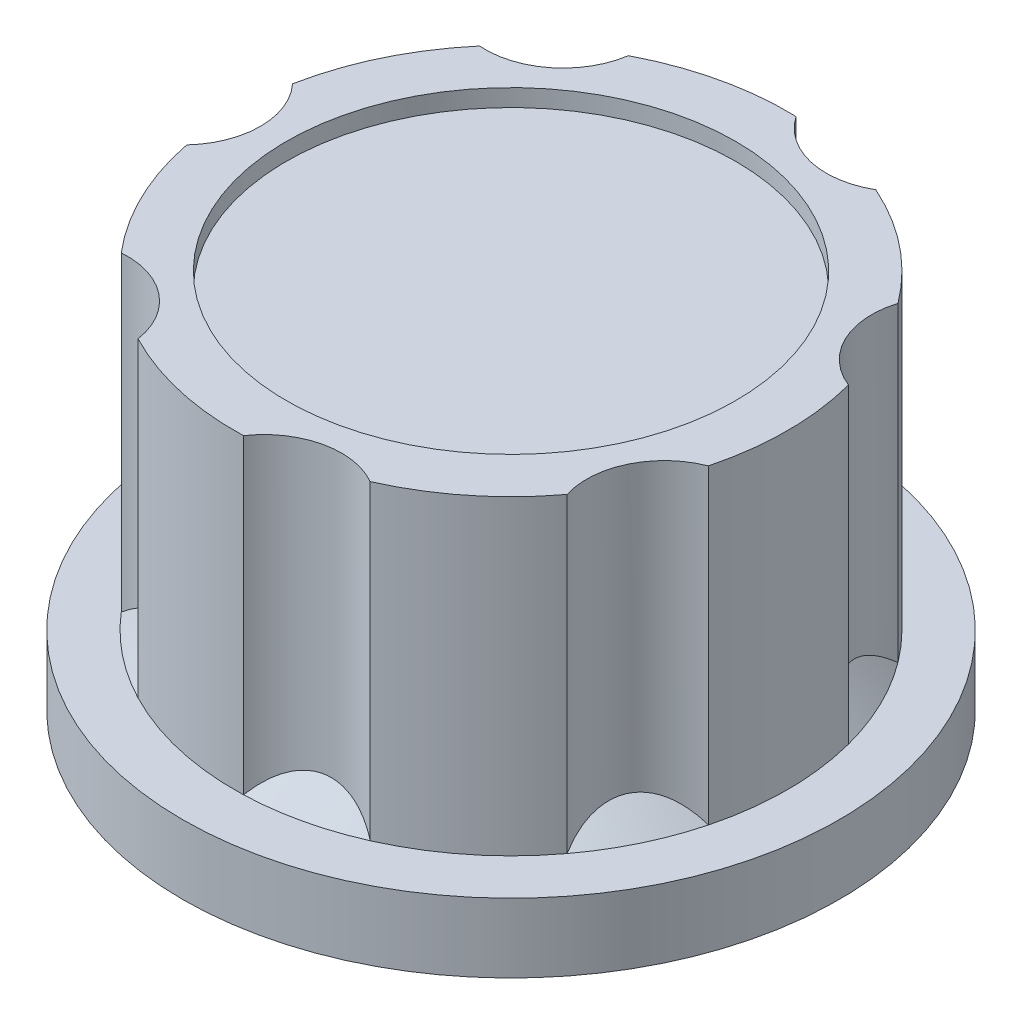
SolidWorks part; units mm, degrees
ref_plane "Front Plane" through (0, 0, 0) normal (0, 0, 1) x (1, 0, 0)
ref_plane "Top Plane" through (0, 0, 0) normal (0, 1, 0) x (1, 0, 0)
ref_plane "Right Plane" through (0, 0, 0) normal (1, 0, 0) x (0, 0, -1)
sketch "Sketch1" plane through (0, 0, 0) normal (1, 0, 0) x (0, 0, -1)
  line L0 (0, 0) -> (-9.5, 0)
  line L1 (-9.5, 0) -> (-9.5, 2)
  line L2 (-9.5, 2) -> (-8, 2)
  line L3 (-8, 2) -> (-8, 11)
  line L4 (-8, 11) -> (-6.5, 11)
  line L5 (0, 0) -> (0, 15) construction
  line L6 (-6.5, 11) -> (-6.5, 10.5)
  line L7 (-6.5, 10.5) -> (0, 10.5)
  line L8 (0, 0) -> (0, 10.5)
  dimension "D1" = 19
  dimension "D2" = 16
  dimension "D3" = 2
  dimension "D4" = 9
  dimension "D5" = 0.5
  dimension "D6" = 1.5
revolve "Revolve1" add sketch "Sketch1" angle 360 about L8
sketch "Sketch2" plane through (0, 0, 0) normal (0, -1, 0) x (1, 0, 0)
  circle A0 centre (0, 0) radius 3.6
  dimension "D1" = 7.2
extrude "Cut-Extrude1" cut sketch "Sketch2" against normal blind 10
sketch "Sketch3" plane through (0, 11, 0) normal (0, 1, 0) x (1, 0, 0)
  circle A0 centre (-9.5, 0) radius 2.25
  circle A1 centre (-5.9232, 7.4274) radius 2.25
  circle A2 centre (2.1139, 9.2618) radius 2.25
  circle A3 centre (8.5592, 4.1219) radius 2.25
  circle A4 centre (8.5592, -4.1219) radius 2.25
  circle A5 centre (2.1139, -9.2618) radius 2.25
  circle A6 centre (-5.9232, -7.4274) radius 2.25
  dimension "D1" = 4.5
  dimension "D2" = 9.5
  dimension "D3" = 7
extrude "Cut-Extrude2" cut sketch "Sketch3" against normal blind 7.5
chamfer "Chamfer1" distance 1.5 angle 45 7 edges at (1.7802, 3.5, 7.7994) (-4.9879, 3.5, 6.2547) (-8, 3.5, 0) (-4.9879, 3.5, -6.2547) (1.7802, 3.5, -7.7994) (7.2078, 3.5, -3.4711) (7.2078, 3.5, 3.4711)
